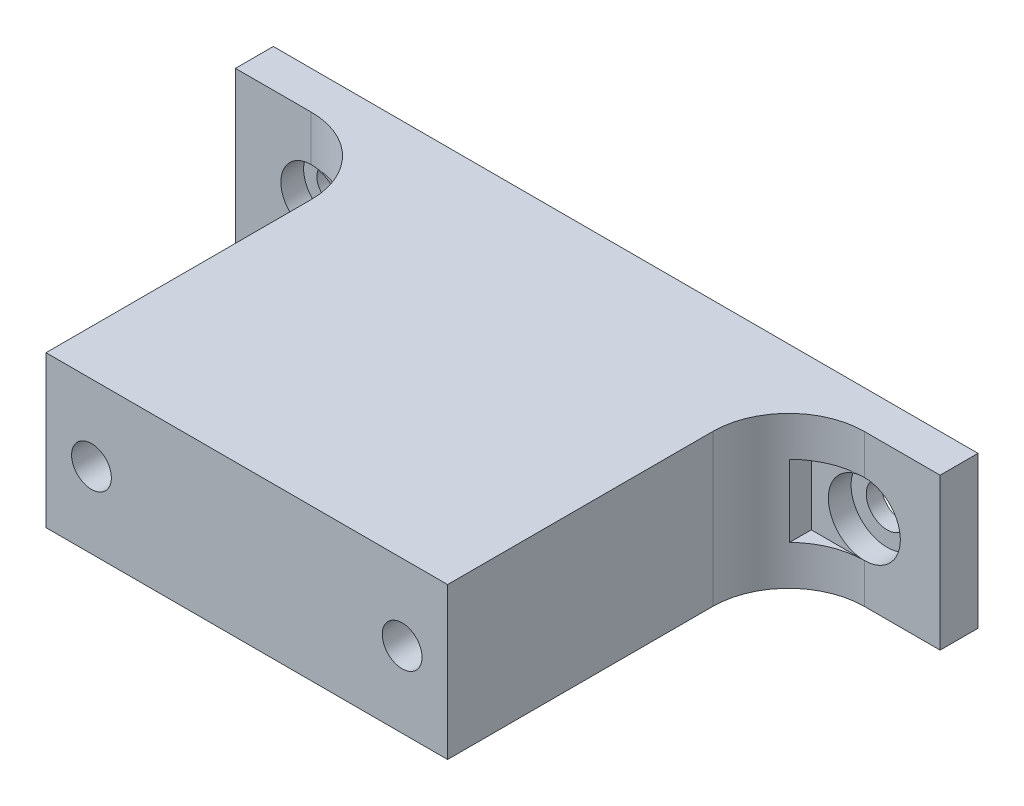
SolidWorks part; units mm, degrees
ref_plane "정면" through (0, 0, 0) normal (0, 0, 1) x (1, 0, 0)
ref_plane "윗면" through (0, 0, 0) normal (0, 1, 0) x (1, 0, 0)
ref_plane "우측면" through (0, 0, 0) normal (1, 0, 0) x (0, 0, -1)
sketch "스케치1" plane through (0, 0, 0) normal (0, 0, 1) x (1, 0, 0)
  line L1 (-26.5, 10) -> (26.5, 10)
  line L2 (-26.5, 10) -> (-26.5, -10)
  line L3 (-26.5, -10) -> (26.5, -10)
  line L4 (26.5, 10) -> (26.5, -10)
  line L5 (-26.5, 10) -> (26.5, -10) construction
  line L6 (-26.5, -10) -> (26.5, 10) construction
  point P0 (0, 0)
  dimension "D1" = 20
  dimension "D2" = 53
extrude "보스-돌출1" add sketch "스케치1" along normal blind 50
hole_wizard "M5 여유 구멍1" positions "스케치2" profile "스케치3" hole size "M5" standard "KS"
sketch "스케치2" plane through (0, 0, 50) normal (0, 0, 1) x (1, 0, 0)
  line L0 (-26.5, 10) -> (-26.5, -10) construction
  line L1 (26.5, -10) -> (26.5, 10) construction
  point P0 (20.5, 0)
  point P2 (-20.5, 0)
  point P9 (0, 0)
  point P11 (0, 0)
  dimension "D1" = 6
  dimension "D2" = 6
sketch "스케치3" plane through (20.5, 0, 50) normal (1, 0, 0) x (0, -1, 0)
  line L0 (0, 0) -> (0, 16.5773)
  line L1 (0, 16.5773) -> (2.625, 15)
  line L2 (2.625, 15) -> (2.625, 0)
  line L5 (2.625, 0) -> (0, 0)
  line L10 (0, 16.5773) -> (-2.625, 15) construction
  line L11 (0, -6.35) -> (0, 107.95) construction
  dimension "구멍 지름" = 5.25
  dimension "구멍 깊이" = 15
  dimension "드릴 각도" = 118
sketch "스케치4" plane through (-26.5, 0, 0) normal (-1, 0, 0) x (0, 0, 1)
  line L0 (50, -10) -> (0, -10) construction
  line L1 (0, 10) -> (5, 10)
  line L2 (0, 10) -> (0, -10)
  line L3 (0, -10) -> (5, -10)
  line L4 (5, 10) -> (5, -10)
  dimension "D1" = 5
extrude "보스-돌출2" add sketch "스케치4" along normal blind 20
hole_wizard "M4 소켓 머리 캡 나사용 카운터보어1" positions "스케치5" profile "스케치6" counterbore size "M4" standard "KS"
sketch "스케치5" plane through (0, 0, 5) normal (0, 0, 1) x (1, 0, 0)
  line L0 (-46.5, -10) -> (-46.5, 10) construction
  line L1 (-46.5, 10) -> (-26.5, 10) construction
  point P0 (-36.5, 0)
  point P9 (-35.8693, -1.9852)
  point P14 (-37.0597, -0.4826)
  dimension "D1" = 10
  dimension "D2" = 10
sketch "스케치6" plane through (-36.5, 0, 5) normal (1, 0, 0) x (0, -1, 0)
  line L0 (0, 0) -> (0, 16.3519)
  line L1 (0, 16.3519) -> (2.25, 15)
  line L2 (2.25, 15) -> (2.25, 3)
  line L3 (2.25, 3) -> (4, 3)
  line L4 (4, 3) -> (4, 0)
  line L5 (4, 0) -> (0, 0)
  line L10 (0, 16.3519) -> (-2.25, 15) construction
  line L11 (0, -6.35) -> (0, 107.95) construction
  dimension "구멍 지름" = 4.5
  dimension "구멍 깊이" = 15
  dimension "카운터보어 지름" = 8
  dimension "카운터보어 깊이" = 3
  dimension "드릴 각도" = 118
sketch "스케치7" plane through (26.5, 0, 0) normal (1, 0, 0) x (0, 0, -1)
  line L0 (-50, -10) -> (0, -10) construction
  line L1 (0, 10) -> (-5, 10)
  line L2 (0, 10) -> (0, -10)
  line L3 (0, -10) -> (-5, -10)
  line L4 (-5, 10) -> (-5, -10)
  dimension "D1" = 5
extrude "보스-돌출3" add sketch "스케치7" along normal blind 20
hole_wizard "M5 소켓 머리 캡 나사용 카운터보어1" positions "스케치8" profile "스케치9" counterbore size "M5" standard "KS"
sketch "스케치8" plane through (0, 0, 5) normal (0, 0, 1) x (1, 0, 0)
  line L0 (46.5, 10) -> (26.5, 10) construction
  line L1 (46.5, 10) -> (46.5, -10) construction
  point P0 (36.5, 0)
  dimension "D1" = 10
  dimension "D2" = 10
sketch "스케치9" plane through (36.5, 0, 5) normal (1, 0, 0) x (0, -1, 0)
  line L0 (0, 0) -> (0, 16.6524)
  line L1 (0, 16.6524) -> (2.75, 15)
  line L2 (2.75, 15) -> (2.75, 3)
  line L3 (2.75, 3) -> (4.75, 3)
  line L4 (4.75, 3) -> (4.75, 0)
  line L5 (4.75, 0) -> (0, 0)
  line L10 (0, 16.6524) -> (-2.75, 15) construction
  line L11 (0, -6.35) -> (0, 107.95) construction
  dimension "구멍 지름" = 5.5
  dimension "구멍 깊이" = 15
  dimension "카운터보어 지름" = 9.5
  dimension "카운터보어 깊이" = 3
  dimension "드릴 각도" = 118
fillet "필렛1" radius 10 2 edges at (26.5, 0, 5) (-26.5, 0, 5)
sketch "스케치10" plane through (0, 0, 5) normal (0, 0, 1) x (1, 0, 0)
  line L1 (-36.5, 4) -> (-30.5, 4)
  line L2 (-36.5, 4) -> (-36.5, -4)
  line L3 (-36.5, -4) -> (-30.5, -4)
  line L4 (-30.5, 4) -> (-30.5, -4)
  line L5 (29.5, 4.75) -> (29.5, -4.75)
  line L6 (36.5, -4.75) -> (29.5, -4.75)
  line L7 (36.5, 4.75) -> (36.5, -4.75)
  line L8 (36.5, 4.75) -> (29.5, 4.75)
  line L9 (36.5, 10) -> (36.5, 4.75) construction
  arc A0 (36.5, 4.75) -> (36.5, -4.75) centre (36.5, 0) ccw construction
  dimension "D1" = 6
  dimension "D2" = 7
extrude "컷-돌출1" cut sketch "스케치10" along normal blind 20
